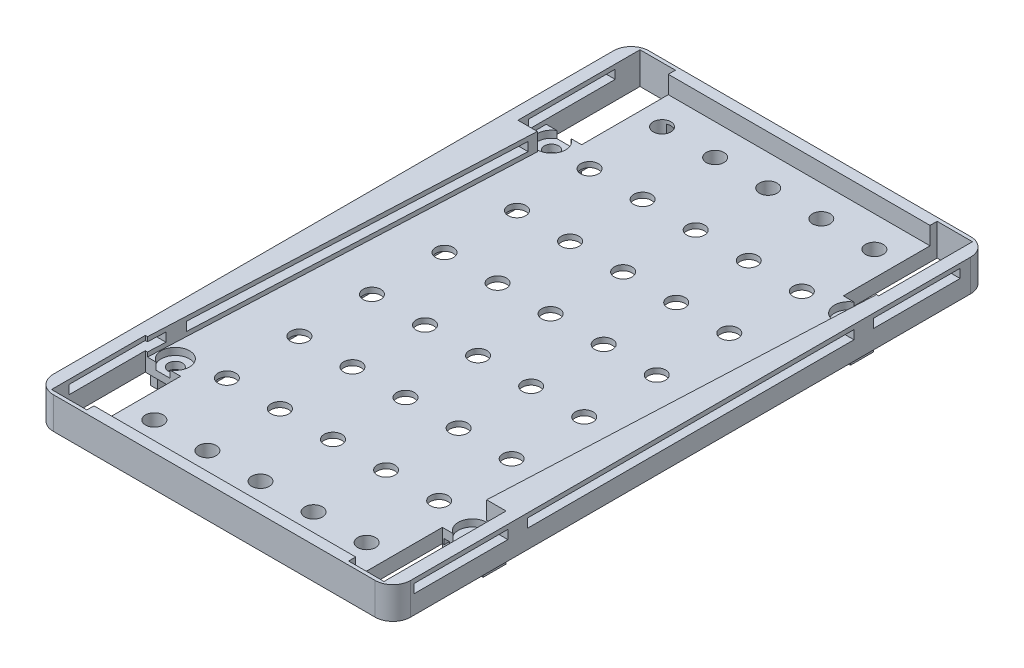
SolidWorks part; units mm, degrees
note: The reader was unsure of these and kept them because the rebuilt part matched: shared geometry of "Sketch4<5>", "Sketch4<6>".
ref_plane "Front Plane" through (0, 0, 0) normal (0, 0, 1) x (1, 0, 0)
ref_plane "Top Plane" through (0, 0, 0) normal (0, 1, 0) x (1, 0, 0)
ref_plane "Right Plane" through (0, 0, 0) normal (1, 0, 0) x (0, 0, -1)
sketch "Sketch1" plane through (0, 0, 0) normal (0, 1, 0) x (1, 0, 0)
  line L0 (-38.7012, 82.4126) -> (48.7961, 82.4126)
  line L1 (48.7961, 82.4126) -> (41.319, -79.9126)
  line L4 (-46.1783, -79.9126) -> (41.319, -79.9126)
  line L5 (-38.7012, 82.4126) -> (-46.1783, -79.9126)
  line L7 (-49.1783, 85.4126) -> (51.7961, 85.4126)
  line L8 (-49.1783, 85.4126) -> (-49.1783, -82.9126)
  line L9 (-49.1783, -82.9126) -> (51.7961, -82.9126)
  line L10 (51.7961, 85.4126) -> (51.7961, -82.9126)
  dimension "D1" = 87.4973
  dimension "D2" = 162.4973
  dimension "D3" = 3
  dimension "D4" = 3
  dimension "D5" = 3
  dimension "D6" = 3
extrude "Boss-Extrude1" add sketch "Sketch1" along normal blind 5
sketch "Sketch2" plane through (0, 0, 0) normal (0, -1, 0) x (1, 0, 0)
  line L1 (-49.1783, 82.9126) -> (51.7961, 82.9126)
  line L2 (-49.1783, 82.9126) -> (-49.1783, -85.4126)
  line L3 (-49.1783, -85.4126) -> (51.7961, -85.4126)
  line L4 (51.7961, 82.9126) -> (51.7961, -85.4126)
extrude "Boss-Extrude2" add sketch "Sketch2" along normal blind 4
sketch "Sketch4" plane through (0, -4, 0) normal (0, -1, 0) x (1, 0, 0)
  line L0 (46.2961, -82.9126) -> (40.2961, -82.9126)
  line L1 (46.2961, -82.9126) -> (46.2961, -49.9126)
  line L2 (46.2961, -49.9126) -> (40.2961, -49.9126)
  line L3 (40.2961, -82.9126) -> (40.2961, -49.9126)
  line L4 (48.2961, -82.9126) -> (38.2961, -82.9126)
  line L5 (48.2961, -82.9126) -> (48.2961, -57.9126)
  line L6 (48.2961, -57.9126) -> (38.2961, -57.9126)
  line L7 (38.2961, -82.9126) -> (38.2961, -57.9126)
  line L8 (46.2961, -49.9126) -> (48.2961, -49.9126)
  line L9 (46.2961, -49.9126) -> (46.2961, -56.4126)
  line L10 (46.2961, -56.4126) -> (48.2961, -56.4126)
  line L11 (48.2961, -49.9126) -> (48.2961, -56.4126)
  line L12 (40.2961, -49.9126) -> (38.2961, -49.9126)
  line L13 (40.2961, -49.9126) -> (40.2961, -56.4126)
  line L14 (40.2961, -56.4126) -> (38.2961, -56.4126)
  line L15 (38.2961, -49.9126) -> (38.2961, -56.4126)
  line L16 (-49.1783, -85.4126) -> (51.7961, -85.4126) construction
  line L18 (51.7961, -85.4126) -> (51.7961, 82.9126) construction
  circle A0 centre (43.2961, -54.4126) radius 2
  point P16 (49.2961, -82.9126)
  dimension "D5" = 4
  dimension "D1" = 33
  dimension "D2" = 6
  dimension "D3" = 3
  dimension "D4" = 4.5
  dimension "D6" = 2
  dimension "D7" = 8
  dimension "D8" = 2
  dimension "D9" = 2.5
  dimension "D10" = 2.5
extrude "Boss-Extrude3" add sketch "Sketch4" along normal blind 4 contours L11 L8 L1 L10
extrude "Cut-Extrude3" cut sketch "Sketch4<5>" against normal blind 124 contours L5 L6 L1 L4 | L1 L6 L3 L0 | L7 L4 L3 L6
sketch "Sketch4<5>" plane through (0, -4, 0) normal (0, -1, 0) x (1, 0, 0) same geometry as "Sketch4"
extrude "Cut-Extrude4" cut sketch "Sketch4<6>" against normal blind 124 contours A0
sketch "Sketch4<6>" plane through (0, -4, 0) normal (0, -1, 0) x (1, 0, 0) same geometry as "Sketch4"
sketch "Sketch6" plane through (0, 0, 0) normal (0, 1, 0) x (1, 0, 0)
  circle A0 centre (43.2961, 54.4126) radius 4
  dimension "D1" = 8
extrude "Cut-Extrude5" cut sketch "Sketch6" against normal blind 2 and the other way blind 19
sketch "Sketch7" plane through (0, -4, 0) normal (0, -1, 0) x (1, 0, 0)
  line L1 (38.2961, -82.9126) -> (48.2961, -82.9126)
  line L2 (38.2961, -82.9126) -> (38.2961, -84.4126)
  line L3 (38.2961, -84.4126) -> (48.2961, -84.4126)
  line L4 (48.2961, -82.9126) -> (48.2961, -84.4126)
  dimension "D1" = 1.5
extrude "Cut-Extrude6" cut sketch "Sketch7" against normal blind 19
sketch "Sketch8" plane through (0, -4, 0) normal (0, -1, 0) x (1, 0, 0)
  line L0 (1.3089, 82.9126) -> (1.3089, -85.4126) construction
  line L1 (51.7961, 82.9126) -> (-49.1783, 82.9126) construction
  line L2 (-49.1783, -85.4126) -> (51.7961, -85.4126) construction
  line L3 (-49.1783, -1.25) -> (51.7961, -1.25) construction
  line L4 (-49.1783, 82.9126) -> (-49.1783, -85.4126) construction
  line L5 (51.7961, -85.4126) -> (51.7961, 82.9126) construction
  line L6 (38.7961, 47.4126) -> (38.7961, 62.4126) construction
  line L7 (-33.1783, 62.4126) -> (35.7961, 62.4126)
  line L8 (-33.1783, 62.4126) -> (-33.1783, -64.9126)
  line L9 (-33.1783, -64.9126) -> (35.7961, -64.9126)
  line L10 (35.7961, 62.4126) -> (35.7961, -64.9126)
  line L11 (-33.1783, 62.4126) -> (35.7961, -64.9126) construction
  line L12 (-33.1783, -64.9126) -> (35.7961, 62.4126) construction
  line L13 (38.7961, 62.4126) -> (40.2961, 62.4126) construction
  point P12 (1.3089, -1.25)
  dimension "D1" = 3
  dimension "D2" = 0
ref_plane "Plane1" through (1.3089, 0, 0) normal (-1, 0, 0) x (0, 0, -1)
ref_plane "Plane2" through (0, 0, -1.25) normal (0, 0, -1) x (1, 0, 0)
mirror "Mirror2" about plane through (0, 0, -1.25) normal (0, 0, -1) of "Cut-Extrude6", "Cut-Extrude5", "Cut-Extrude4", "Cut-Extrude3", "Boss-Extrude3"
mirror "Mirror3" about plane through (1.3089, 0, 0) normal (-1, 0, 0) of "Mirror2", "Cut-Extrude6", "Cut-Extrude5", "Cut-Extrude4", "Cut-Extrude3", "Boss-Extrude3"
sketch "Sketch10" plane through (0, -4, 0) normal (0, -1, 0) x (1, 0, 0)
  line L0 (46.2961, -56.4126) -> (38.7961, -56.4126)
  line L1 (46.2961, -49.9126) -> (48.2961, -49.9126) construction
  line L2 (38.7961, -56.4126) -> (36.7961, -56.4126)
  line L3 (38.7961, -56.4126) -> (38.7961, -49.9126)
  line L4 (38.7961, -49.9126) -> (36.7961, -49.9126)
  line L5 (36.7961, -56.4126) -> (36.7961, -49.9126)
  dimension "D1" = 7.5
  dimension "D2" = 0
  dimension "D3" = 2
extrude "Boss-Extrude4" add sketch "Sketch10" along normal up to surface (4 mm away) contours L5 L2 L3 L4 up to face at (47.2961, -8, -53.1626)
mirror "Mirror4" about plane through (1.3089, 0, 0) normal (-1, 0, 0) of "Boss-Extrude4"
mirror "Mirror5" about plane through (0, 0, -1.25) normal (0, 0, -1) of "Boss-Extrude4", "Mirror4"
extrude "Cut-Extrude7" cut sketch "Sketch8" against normal blind 2.5
fillet "Fillet1" radius 5 1 edges at (51.7961, 0.5, -85.4126)
fillet "Fillet2" radius 5 1 edges at (-49.1783, 0.5, -85.4126)
fillet "Fillet3" radius 5 1 edges at (51.7961, 0.5, 82.9126)
fillet "Fillet4" radius 5 1 edges at (-49.1783, 0.5, 82.9126)
sketch "Sketch12" plane through (0, 0, -85.4126) normal (0, 0, -1) x (-1, 0, 0)
  line L0 (44.1783, -4) -> (-46.7961, -4) construction
  line L1 (-26.7961, -4) -> (24.1783, -4)
  line L2 (-26.7961, -4) -> (-26.7961, -2)
  line L3 (-26.7961, -2) -> (24.1783, -2)
  line L4 (24.1783, -4) -> (24.1783, -2)
  line L5 (49.1783, 5) -> (49.1783, -4) construction
  line L6 (-51.7961, -4) -> (-51.7961, 5) construction
  dimension "D1" = 25
  dimension "D2" = 25
  dimension "D3" = 2
extrude "Boss-Extrude6" add sketch "Sketch12" along normal blind 17.5
sketch "Sketch13" plane through (0, -4, 0) normal (0, -1, 0) x (1, 0, 0)
  line L1 (-24.1783, -102.9126) -> (26.7961, -102.9126)
  line L2 (-24.1783, -102.9126) -> (-24.1783, -104.4126)
  line L3 (-24.1783, -104.4126) -> (26.7961, -104.4126)
  line L4 (26.7961, -102.9126) -> (26.7961, -104.4126)
  dimension "D1" = 1.5
extrude "Boss-Extrude7" add sketch "Sketch13" against normal blind 20
sketch "Sketch14" plane through (0, 5, 0) normal (0, 1, 0) x (1, 0, 0)
  line L1 (-45.6783, 57.9126) -> (-40.1737, 57.9126)
  line L2 (-45.6783, 57.9126) -> (-45.6783, 49.9126)
  line L3 (-45.6783, 49.9126) -> (-40.1737, 49.9126)
  line L4 (-40.1737, 57.9126) -> (-40.1737, 49.9126)
  dimension "D1" = 8
extrude "Cut-Extrude11" cut sketch "Sketch14" against normal up to surface (5 mm away) up to face at (1.3089, 0, -1.25)
sketch "Sketch15" plane through (0, 5, 0) normal (0, 1, 0) x (1, 0, 0)
  line L1 (48.2961, -55.4126) -> (42.7915, -55.4126)
  line L2 (48.2961, -55.4126) -> (48.2961, -47.4126)
  line L3 (48.2961, -47.4126) -> (42.7915, -47.4126)
  line L4 (42.7915, -55.4126) -> (42.7915, -47.4126)
  arc A2 (42.7915, -47.9446) -> (41.3596, -55.4126) centre (43.2961, -51.9126) ccw construction
  dimension "D1" = 4.5
extrude "Cut-Extrude13" cut sketch "Sketch15" against normal up to surface (5 mm away) up to face at (-5.3878, 0, -8.606)
sketch "Sketch16" plane through (0, -4, 0) normal (0, -1, 0) x (1, 0, 0)
  line L1 (-36.1783, 47.4126) -> (-37.6783, 47.4126)
  line L2 (-36.1783, 47.4126) -> (-36.1783, 56.6039)
  line L3 (-36.1783, 56.6039) -> (-37.6783, 56.6039)
  line L4 (-37.6783, 47.4126) -> (-37.6783, 56.6039)
  line L5 (38.7961, 56.0363) -> (40.2961, 56.0363)
  line L6 (38.7961, 56.0363) -> (38.7961, 47.4126)
  line L7 (38.7961, 47.4126) -> (40.2961, 47.4126)
  line L8 (40.2961, 56.0363) -> (40.2961, 47.4126)
  line L9 (-36.1783, -61.0582) -> (-37.6783, -61.0582)
  line L10 (-36.1783, -61.0582) -> (-36.1783, -49.9126)
  line L11 (-36.1783, -49.9126) -> (-37.6783, -49.9126)
  line L12 (-37.6783, -61.0582) -> (-37.6783, -49.9126)
  line L13 (38.7961, -49.9126) -> (40.2961, -49.9126)
  line L14 (38.7961, -49.9126) -> (38.7961, -63.4377)
  line L15 (38.7961, -63.4377) -> (40.2961, -63.4377)
  line L16 (40.2961, -49.9126) -> (40.2961, -63.4377)
  dimension "D1" = 1.5
  dimension "D2" = 1.5
  dimension "D3" = 1.5
  dimension "D4" = 1.5
extrude "Cut-Extrude15" cut sketch "Sketch16" against normal blind 1.5
sketch "Sketch17" plane through (0, -4, 0) normal (0, -1, 0) x (1, 0, 0)
  line L0 (-33.1783, -64.9126) -> (35.7961, -64.9126) construction
  line L1 (-29.6783, -64.9126) -> (-26.6783, -64.9126)
  line L2 (-29.6783, -64.9126) -> (-29.6783, -85.4126)
  line L3 (-29.6783, -85.4126) -> (-26.6783, -85.4126)
  line L4 (-26.6783, -64.9126) -> (-26.6783, -85.4126)
  line L5 (-44.1783, -85.4126) -> (-24.1783, -85.4126) construction
  line L6 (-24.1783, -104.4126) -> (-24.1783, -85.4126) construction
  dimension "D1" = 2.5
  dimension "D2" = 3
extrude "Cut-Extrude16" cut sketch "Sketch17" against normal blind 3
sketch "Sketch18" plane through (0, 0, -104.4126) normal (0, 0, -1) x (-1, 0, 0)
  line L0 (24.1783, 16) -> (-26.7961, 16) construction
  line L1 (-26.7961, 16) -> (-24.2961, 16)
  line L2 (-26.7961, 16) -> (-26.7961, -4.6825)
  line L3 (-26.7961, -4.6825) -> (-24.2961, -4.6825)
  line L4 (-24.2961, 16) -> (-24.2961, -4.6825)
  line L5 (24.1783, -4) -> (21.6783, -4)
  line L6 (24.1783, -4) -> (24.1783, 16)
  line L7 (24.1783, 16) -> (21.6783, 16)
  line L8 (21.6783, -4) -> (21.6783, 16)
  line L9 (24.1783, -4) -> (-26.7961, -4) construction
  line L10 (-8.7961, 16) -> (6.1783, 16)
  line L11 (-8.7961, 16) -> (-8.7961, -4)
  line L12 (-8.7961, -4) -> (6.1783, -4)
  line L13 (6.1783, 16) -> (6.1783, -4)
  dimension "D1" = 2.5
  dimension "D2" = 2.5
  dimension "D3" = 18
  dimension "D4" = 18
extrude "Cut-Extrude18" cut sketch "Sketch18" against normal up to surface (19 mm away) up to face at (-8.5202, -1.6667, -85.4126)
sketch "Sketch19" plane through (-21.6783, 0, 0) normal (-1, 0, 0) x (0, 0, 1)
  line L0 (-86.4126, -2) -> (-85.4126, -2)
  line L1 (-102.9126, -2) -> (-85.4126, -2) construction
  line L2 (-85.4126, -4) -> (-85.4126, 5) construction
  line L3 (-85.4126, -2) -> (-85.4126, -1)
  line L4 (-85.4126, -1) -> (-86.4126, -2)
  line L5 (-102.9126, -2) -> (-101.9126, -2)
  line L6 (-101.9126, -2) -> (-102.9126, -1)
  line L7 (-102.9126, -2) -> (-102.9126, 16) construction
  line L8 (-102.9126, -1) -> (-102.9126, -2)
  dimension "D1" = 1
  dimension "D2" = 1
  dimension "D3" = 1
  dimension "D4" = 1
extrude "Boss-Extrude8" add sketch "Sketch19" against normal up to surface (45.9745 mm away)
sketch "Sketch20" plane through (0, 0, -104.4126) normal (0, 0, -1) x (-1, 0, 0)
  line L0 (6.1783, -4) -> (6.1783, 16) construction
  line L1 (-8.7961, -4) -> (6.1783, -4)
  line L2 (-8.7961, -4) -> (-8.7961, 1.7659)
  line L3 (-8.7961, 1.7659) -> (6.1783, 1.7659)
  line L4 (6.1783, -4) -> (6.1783, 1.7659)
extrude "Cut-Extrude19" cut sketch "Sketch20" against normal up to surface (19 mm away) up to face at (1.3089, -3, -85.4126)
sketch "Sketch21" plane through (51.7961, 0, 0) normal (1, 0, 0) x (0, 0, -1)
  line L3 (-79.9126, 2.5) -> (82.4126, 2.5) construction
  line L8 (-79.9126, 0) -> (-79.9126, 5) construction
  line L9 (82.4126, 5) -> (82.4126, 0) construction
  line L14 (49.9126, 5) -> (49.9126, 0) construction
  line L15 (47.4126, 1.25) -> (-44.9126, 1.25)
  line L20 (47.4126, 1.25) -> (47.4126, 3.75)
  line L21 (47.4126, 3.75) -> (-44.9126, 3.75)
  line L26 (-44.9126, 1.25) -> (-44.9126, 3.75)
  line L27 (47.4126, 1.25) -> (-44.9126, 3.75) construction
  line L32 (47.4126, 3.75) -> (-44.9126, 1.25) construction
  point P0 (1.25, 2.5)
  dimension "D1" = 2.5
  dimension "D3" = 2.5
extrude "Cut-Extrude21" cut sketch "Sketch21" against normal blind 151
sketch "Sketch22" plane through (0, 0, 0) normal (0, 1, 0) x (1, 0, 0)
  line L0 (-35.6783, 73.6626) -> (38.2961, 73.6626) construction
  line L1 (-35.6783, 82.4126) -> (-35.6783, 57.9126) construction
  line L2 (38.2961, 82.4126) -> (38.2961, 57.9126) construction
  line L3 (-35.6783, 82.4126) -> (-35.6783, 64.9126) construction
  line L4 (1.3089, 73.6626) -> (1.3089, 45.8107) construction
  circle A0 centre (1.3089, 73.6626) radius 2.5
  circle A1 centre (16.3089, 73.6626) radius 2.5
  circle A2 centre (31.3089, 73.6626) radius 2.5
  circle A3 centre (-28.6911, 73.6626) radius 2.5
  circle A4 centre (-13.6911, 73.6626) radius 2.5
  point P8 (1.3089, -79.9126)
  point P10 (-35.6783, 73.6626)
  dimension "D1" = 5
  dimension "D2" = 3
extrude "Cut-Extrude22" cut sketch "Sketch22" against normal blind 151
pattern_linear "LPattern1" count 8 spacing 20.5 along (0, 0, 1) of "Cut-Extrude22"
sketch "Sketch23" plane through (0, 0, 0) normal (0, 1, 0) x (1, 0, 0)
  line L0 (-46.1783, -79.9126) -> (-45.6783, -79.9126)
  line L1 (-45.6783, -79.9126) -> (-45.6783, -69.0578)
  line L2 (-45.6783, -69.0578) -> (-46.1783, -79.9126)
  line L3 (48.2961, 82.4126) -> (48.7961, 82.4126)
  line L4 (48.7961, 82.4126) -> (48.2961, 71.5578)
  line L5 (48.2961, 71.5578) -> (48.2961, 82.4126)
extrude "Boss-Extrude9" add sketch "Sketch23" along normal up to surface (5 mm away) up to face at (1.3089, 5, -1.25)
sketch "Sketch24" plane through (0, 0, 53.9126) normal (0, 0, 1) x (1, 0, 0)
  line L0 (-34.1783, -4) -> (-33.1783, -4)
  line L1 (46.7961, -4) -> (-44.1783, -4) construction
  line L2 (-33.1783, -4) -> (-34.1783, -5)
  line L3 (-34.1783, -8) -> (-34.1783, -4) construction
  line L4 (-34.1783, -5) -> (-34.1783, -4)
  line L5 (-46.6783, -4) -> (-45.6783, -5)
  line L6 (-49.1783, -4) -> (-44.1783, -4) construction
  line L7 (-45.6783, -8) -> (-45.6783, -4) construction
  line L8 (-45.6783, -5) -> (-45.6783, -4)
  line L9 (-45.6783, -4) -> (-46.6783, -4)
  dimension "D1" = 1
  dimension "D2" = 1
  dimension "D3" = 1
  dimension "D4" = 1
extrude "Boss-Extrude10" add sketch "Sketch24" against normal up to surface (6.5 mm away) up to face at (-44.6783, -6, 47.4126)
mirror "Mirror7" about plane through (1.3089, 0, 0) normal (-1, 0, 0) of "Boss-Extrude10"
sketch "Sketch27" plane through (0, 0, -56.4126) normal (0, 0, -1) x (-1, 0, 0)
  line L0 (45.6783, -5) -> (45.6783, -4)
  line L1 (45.6783, -4) -> (46.6783, -4)
  line L2 (44.1783, -4) -> (49.1783, -4) construction
  line L3 (46.6783, -4) -> (45.6783, -5)
  line L4 (33.1783, -4) -> (34.1783, -4)
  line L5 (34.1783, -4) -> (34.1783, -5)
  line L6 (34.1783, -5) -> (33.1783, -4)
  line L7 (-36.7961, -5) -> (-36.7961, -4)
  line L8 (-36.7961, -4) -> (-35.7961, -4)
  line L9 (-35.7961, -4) -> (-36.7961, -5)
  line L10 (-49.2961, -4) -> (-48.2961, -5)
  line L11 (-48.2961, -5) -> (-48.2961, -4)
  line L12 (-48.2961, -4) -> (-49.2961, -4)
extrude "Boss-Extrude11" add sketch "Sketch27" against normal up to surface (6.5 mm away) up to face at (37.7961, -6, -49.9126)
sketch "Sketch28" plane through (-49.1783, 0, 0) normal (-1, 0, 0) x (0, 0, 1)
  line L0 (-49.9126, 0) -> (-49.9126, 5) construction
  line L1 (50.4126, 1.25) -> (76.9126, 1.25)
  line L2 (50.4126, 1.25) -> (50.4126, 3.75)
  line L3 (50.4126, 3.75) -> (76.9126, 3.75)
  line L4 (76.9126, 1.25) -> (76.9126, 3.75)
  line L5 (-52.9126, 1.25) -> (-77.4126, 1.25)
  line L6 (-52.9126, 1.25) -> (-52.9126, 3.75)
  line L7 (-52.9126, 3.75) -> (-77.4126, 3.75)
  line L8 (-77.4126, 1.25) -> (-77.4126, 3.75)
  line L9 (-80.4126, 5) -> (-80.4126, -4) construction
  line L10 (47.4126, 5) -> (47.4126, 0) construction
  line L11 (79.9126, 0) -> (79.9126, 5) construction
  dimension "D1" = 3
  dimension "D2" = 3
  dimension "D3" = 3
  dimension "D4" = 3
extrude "Cut-Extrude23" cut sketch "Sketch28" against normal blind 124
sketch "Sketch29" plane through (0, -4, 0) normal (0, -1, 0) x (1, 0, 0)
  line L0 (-44.1783, -85.4126) -> (-29.6783, -85.4126) construction
  line L1 (-43.4751, -85.4126) -> (45.1455, -85.4126)
  line L2 (-43.4751, -85.4126) -> (-43.4751, -109.4549)
  line L3 (-43.4751, -109.4549) -> (45.1455, -109.4549)
  line L4 (45.1455, -85.4126) -> (45.1455, -109.4549)
extrude "Cut-Extrude24" cut sketch "Sketch29" against normal blind 60
